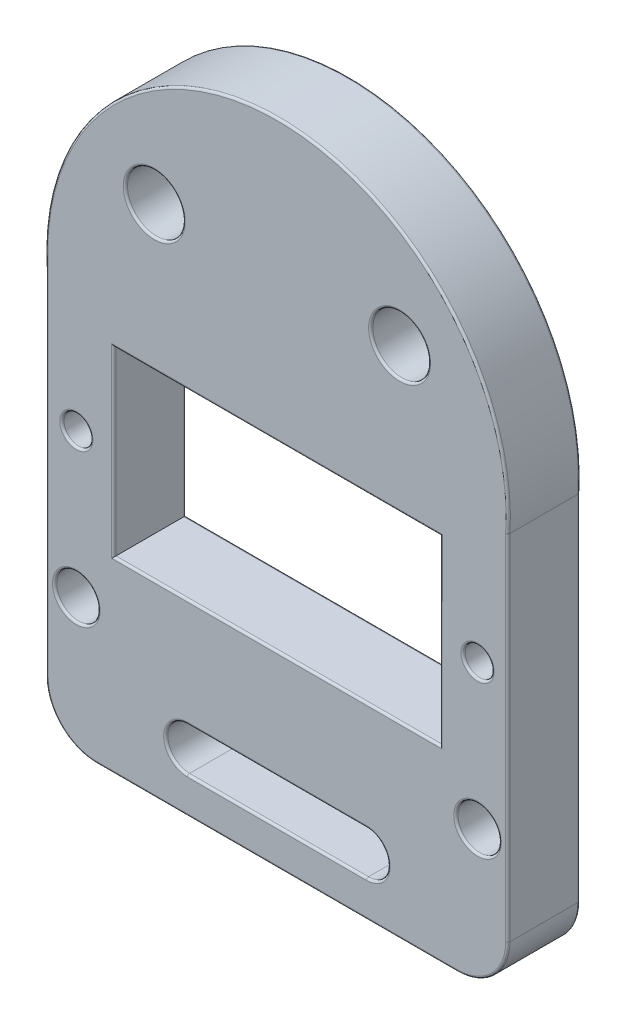
SolidWorks part; units mm, degrees
ref_plane "Front Plane" through (0, 0, 0) normal (0, 0, 1) x (1, 0, 0)
ref_plane "Top Plane" through (0, 0, 0) normal (0, 1, 0) x (1, 0, 0)
ref_plane "Right Plane" through (0, 0, 0) normal (1, 0, 0) x (0, 0, -1)
sketch "Sketch1" plane through (0, 0, 0) normal (0, 0, 1) x (1, 0, 0)
  line L0 (0, 25.7) -> (0, -19.3) construction
  line L1 (-11.3, -6.3) -> (11.3, -6.3)
  line L2 (-11.3, -6.3) -> (-11.3, 6.3)
  line L3 (-11.3, 6.3) -> (11.3, 6.3)
  line L4 (11.3, -6.3) -> (11.3, 6.3)
  line L5 (-11.3, -6.3) -> (11.3, 6.3) construction
  line L6 (-11.3, 6.3) -> (11.3, -6.3) construction
  line L7 (-6.2, -15.3) -> (6.2, -15.3) construction
  line L8 (-6.2, -13.8) -> (6.2, -13.8)
  line L9 (-6.2, -16.8) -> (6.2, -16.8)
  line L11 (-16, 8.7) -> (16, 8.7) construction
  line L12 (-16, 8.7) -> (-16, -19.3)
  line L13 (-16, -19.3) -> (16, -19.3)
  line L14 (16, 8.7) -> (16, -19.3)
  circle A0 centre (-13.9, 0) radius 1
  circle A1 centre (-13.9, -10) radius 1.5
  arc A2 (-6.2, -13.8) -> (-6.2, -16.8) centre (-6.2, -15.3) ccw
  arc A3 (6.2, -16.8) -> (6.2, -13.8) centre (6.2, -15.3) ccw
  circle A4 centre (-8.5, 16.3) radius 2
  circle A5 centre (8.5, 16.3) radius 2
  circle A6 centre (13.9, 0) radius 1
  circle A7 centre (13.9, -10) radius 1.5
  arc A8 (-16, 8.7) -> (16, 8.7) centre (0, 9.6706) cw
  point P0 (0, 0)
  point P14 (0, -15.3)
  point P25 (0, 25.7)
  point P33 (0, 0)
  point P34 (0, 0)
  point P35 (11.3, 0)
  dimension "D3" = 2
  dimension "D6" = 3
  dimension "D10" = 1.5
  dimension "D12" = 4
  dimension "D1" = 22.6
  dimension "D2" = 12.6
  dimension "D4" = 2.6
  dimension "D7" = 10
  dimension "D8" = 12.4
  dimension "D9" = 4
  dimension "D11" = 45
  dimension "D13" = 8.5
  dimension "D14" = 10
  dimension "D15" = 28
  dimension "D16" = 32
  dimension "D17" = 13
extrude "Boss-Extrude1" add sketch "Sketch1" along normal blind 5
fillet "Fillet1" radius 3.5 2 edges at (16, -19.3, 2.5) (-16, -19.3, 2.5)
fillet "Fillet2" radius 0.15 40 edges at (12.4, -10, 0) (6.5, 16.3, 0) (7.7, -15.3, 0) (0, -16.8, 0) (-7.7, -15.3, 0) (0, -13.8, 0) (-12.4, -10, 0) (-11.3, 0, 0) (0, 6.3, 0) (11.3, 0, 0) (0, -6.3, 0) (0, 25.7, 0) (-16, -3.55, 0) (-14.9749, -18.2749, 0) (0, -19.3, 0) (14.9749, -18.2749, 0) (16, -3.55, 0) (-12.9, 0, 0) (-6.5, 16.3, 0) (12.9, 0, 0) (12.4, -10, 5) (12.9, 0, 5) (6.5, 16.3, 5) (-6.5, 16.3, 5) (0, -16.8, 5) (7.7, -15.3, 5) (0, -13.8, 5) (-7.7, -15.3, 5) (-14.9749, -18.2749, 5) (-16, -3.55, 5) (0, 25.7, 5) (16, -3.55, 5) (14.9749, -18.2749, 5) (0, -19.3, 5) (0, 6.3, 5) (-11.3, 0, 5) (0, -6.3, 5) (11.3, 0, 5) (-12.9, 0, 5) (-12.4, -10, 5)
